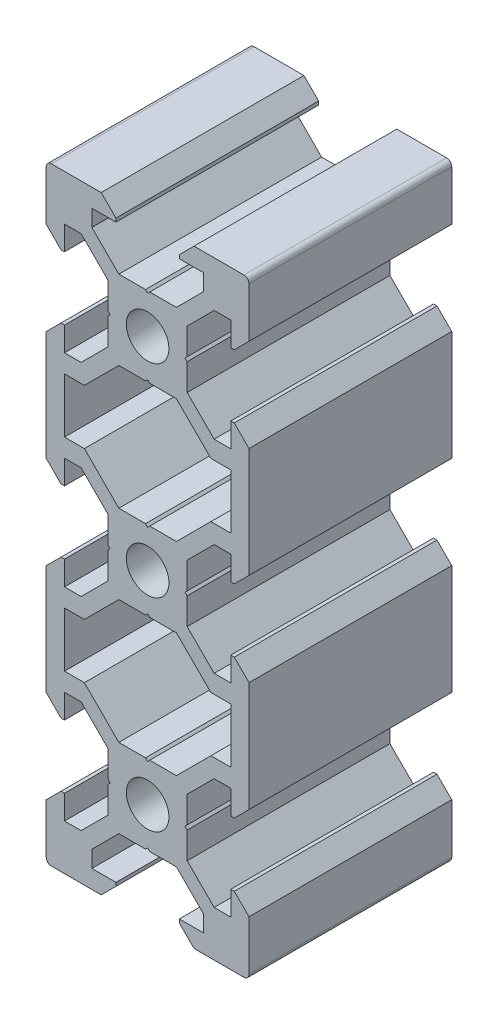
SolidWorks part; units mm, degrees
ref_plane "Plan de face" through (0, 0, 0) normal (0, 0, 1) x (1, 0, 0)
ref_plane "Plan de dessus" through (0, 0, 0) normal (0, 1, 0) x (1, 0, 0)
ref_plane "Plan de droite" through (0, 0, 0) normal (1, 0, 0) x (0, 0, -1)
ref_axis "Axe" through (0, 0, -13.782) along (0, 0, 1)
sketch "Esquisse1" plane through (0, 0, 0) normal (0, 0, 1) x (1, 0, 0)
  line L0 (0, 27.6392) -> (0, -27.6392) construction
  line L1 (-33.6074, 0) -> (33.6074, 0) construction
  line L2 (0, 0) -> (-22.2114, 22.2114) construction
  line L3 (-9.5, 10) -> (-4.58, 10)
  line L4 (-4.58, 10) -> (-3.125, 8.545)
  line L5 (-3.125, 8.545) -> (-3.125, 8.2)
  line L6 (-3.125, 8.2) -> (-5.5, 8.2)
  line L7 (-2.8393, 3.9) -> (-5.5, 6.5607)
  line L8 (-2.8393, 3.9) -> (-0.21, 3.9)
  line L9 (-5.5, 6.5607) -> (-5.5, 8.2)
  line L10 (0, 3.69) -> (0, 2.1)
  line L11 (-3.9, 2.8393) -> (-6.5607, 5.5)
  line L12 (-8.545, 3.125) -> (-8.2, 3.125)
  line L13 (-8.2, 3.125) -> (-8.2, 5.5)
  line L14 (-6.5607, 5.5) -> (-8.2, 5.5)
  line L15 (-10, 4.58) -> (-8.545, 3.125)
  line L16 (-10, 9.5) -> (-10, 4.58)
  line L17 (-0.21, 3.9) -> (0, 3.69)
  line L18 (-3.9, 2.8393) -> (-3.9, 0.21)
  line L19 (-6.2393, -12.7) -> (-8.2, -12.7)
  line L20 (-3.9, 0.21) -> (-3.69, 0)
  line L21 (-0.21, -3.9) -> (0, -3.69)
  line L22 (0, -3.69) -> (0, -2.1)
  line L23 (-6.5607, -5.5) -> (-8.2, -5.5)
  line L24 (-2.8393, -3.9) -> (-0.21, -3.9)
  line L25 (-8.545, -3.125) -> (-8.2, -3.125)
  line L26 (-10, -4.58) -> (-8.545, -3.125)
  line L27 (-8.2, -3.125) -> (-8.2, -5.5)
  line L28 (-2.8393, -3.9) -> (-6.2393, -7.3)
  line L29 (-3.9, -2.8393) -> (-6.5607, -5.5)
  line L30 (-3.9, -2.8393) -> (-3.9, -0.21)
  line L31 (-3.9, -0.21) -> (-3.69, 0)
  line L32 (-6.2393, -7.3) -> (-8.2, -7.3)
  line L33 (-8.2, -7.3) -> (-8.2, -12.7)
  line L34 (-8.2, -10) -> (-10, -10) construction
  line L35 (-10, -15.42) -> (-10, -4.58)
  line L36 (-3.9, -19.79) -> (-3.69, -20)
  line L37 (-3.9, -17.1607) -> (-3.9, -19.79)
  line L38 (-3.9, -17.1607) -> (-6.5607, -14.5)
  line L39 (-2.8393, -16.1) -> (-6.2393, -12.7)
  line L40 (-8.2, -16.875) -> (-8.2, -14.5)
  line L41 (-10, -15.42) -> (-8.545, -16.875)
  line L42 (-8.545, -16.875) -> (-8.2, -16.875)
  line L43 (-2.8393, -16.1) -> (-0.21, -16.1)
  line L44 (-6.5607, -14.5) -> (-8.2, -14.5)
  line L45 (0, -16.31) -> (0, -17.9)
  line L46 (-0.21, -16.1) -> (0, -16.31)
  line L47 (-8.2, -30) -> (-10, -30) construction
  line L48 (-3.69, -20) -> (0, -20) construction
  line L49 (-0.21, -23.9) -> (0, -23.69)
  line L50 (0, -23.69) -> (0, -22.1)
  line L51 (-6.5607, -25.5) -> (-8.2, -25.5)
  line L52 (-2.8393, -23.9) -> (-0.21, -23.9)
  line L53 (-8.545, -23.125) -> (-8.2, -23.125)
  line L54 (-10, -24.58) -> (-8.545, -23.125)
  line L55 (-8.2, -23.125) -> (-8.2, -25.5)
  line L56 (-2.8393, -23.9) -> (-6.2393, -27.3)
  line L57 (-3.9, -22.8393) -> (-6.5607, -25.5)
  line L58 (-3.9, -22.8393) -> (-3.9, -20.21)
  line L59 (-3.9, -20.21) -> (-3.69, -20)
  line L60 (-10, -24.58) -> (-10, -35.42)
  line L61 (-8.2, -32.7) -> (-8.2, -27.3)
  line L62 (-6.2393, -32.7) -> (-8.2, -32.7)
  line L63 (-3.9, -39.79) -> (-3.69, -40)
  line L64 (-3.9, -37.1607) -> (-3.9, -39.79)
  line L65 (-3.9, -37.1607) -> (-6.5607, -34.5)
  line L66 (-2.8393, -36.1) -> (-6.2393, -32.7)
  line L67 (-8.2, -36.875) -> (-8.2, -34.5)
  line L68 (-10, -35.42) -> (-8.545, -36.875)
  line L69 (-8.545, -36.875) -> (-8.2, -36.875)
  line L70 (-2.8393, -36.1) -> (-0.21, -36.1)
  line L71 (-6.5607, -34.5) -> (-8.2, -34.5)
  line L72 (0, -36.31) -> (0, -37.9)
  line L73 (-0.21, -36.1) -> (0, -36.31)
  line L74 (-3.9, -40.21) -> (-3.69, -40)
  line L75 (-6.2393, -27.3) -> (-8.2, -27.3)
  line L76 (-3.9, -42.8393) -> (-3.9, -40.21)
  line L77 (-0.21, -43.9) -> (0, -43.69)
  line L78 (-10, -49.5) -> (-10, -44.58)
  line L79 (-10, -44.58) -> (-8.545, -43.125)
  line L80 (-6.5607, -45.5) -> (-8.2, -45.5)
  line L81 (-8.2, -43.125) -> (-8.2, -45.5)
  line L82 (-8.545, -43.125) -> (-8.2, -43.125)
  line L83 (-3.9, -42.8393) -> (-6.5607, -45.5)
  line L84 (0, -43.69) -> (0, -42.1)
  line L85 (-5.5, -46.5607) -> (-5.5, -48.2)
  line L86 (-2.8393, -43.9) -> (-0.21, -43.9)
  line L87 (-2.8393, -43.9) -> (-5.5, -46.5607)
  line L88 (-3.125, -48.2) -> (-5.5, -48.2)
  line L89 (-3.125, -48.545) -> (-3.125, -48.2)
  line L90 (-4.58, -50) -> (-3.125, -48.545)
  line L91 (-9.5, -50) -> (-4.58, -50)
  arc A0 (0, -2.1) -> (0, 2.1) centre (0, 0) cw
  arc A1 (-9.5, 10) -> (-10, 9.5) centre (-9.5, 9.5) ccw
  arc A2 (0, -37.9) -> (0, -42.1) centre (0, -40) ccw
  arc A3 (-9.5, -50) -> (-10, -49.5) centre (-9.5, -49.5) cw
  arc A4 (0, -17.9) -> (0, -22.1) centre (0, -20) ccw
  point P4 (0, 0)
  point P7 (0, 0)
  point P30 (-10, 10)
  point P60 (0, -20)
  point P111 (-10, -50)
  dimension "D5" = 11
  dimension "D2" = 2.1
  dimension "D3" = 6.25
  dimension "D10" = 0.5
  dimension "D4" = 9.16
  dimension "D6" = 1.5
  dimension "D7" = 1.8
  dimension "D8" = 4.3
  dimension "D9" = 20
  dimension "D11" = 0.42
  dimension "D12" = 10
  dimension "D13" = 1.8
extrude "Boss.-Extru.1" add sketch "Esquisse1" along normal blind 20
sketch "Esquisse3" plane through (0, 0, 20) normal (0, 0, 1) x (1, 0, 0)
  line L0 (0, 0) -> (-9.8536, 9.8536) construction
  line L1 (-8.2, 8.2) -> (-8.2, 6.57)
  line L2 (-8.2, 6.57) -> (-7.54, 6.57)
  line L3 (-7.54, 6.57) -> (-6.57, 7.54)
  line L4 (-8.2, 3.125) -> (-8.2, 5.5) construction
  line L5 (-6.57, 8.2) -> (-6.57, 7.54)
  line L6 (-8.2, 8.2) -> (-6.57, 8.2)
  line L7 (-5.5, 6.5607) -> (-5.5, 8.2) construction
  line L8 (-3.69, -20) -> (0, -20) construction
  line L9 (-8.2, -48.2) -> (-6.57, -48.2)
  line L10 (-6.57, -48.2) -> (-6.57, -47.54)
  line L11 (-7.54, -46.57) -> (-6.57, -47.54)
  line L12 (-8.2, -46.57) -> (-7.54, -46.57)
  line L13 (-8.2, -48.2) -> (-8.2, -46.57)
  arc A0 (-9.5, 10) -> (-10, 9.5) centre (-9.5, 9.5) ccw construction
  point P13 (-7.055, 7.055)
  point P14 (-6.57, 7.87)
  point P26 (-7.055, -47.055)
  dimension "D1" = 1.07
extrude "Enlèv. mat.-Extru.1" [suppressed] cut sketch "Esquisse3" against normal through all
mirror "Symétrie1" about plane through (0, 3.69, 20) normal (-1, 0, 0) of "Enlèv. mat.-Extru.1", "Boss.-Extru.1"
